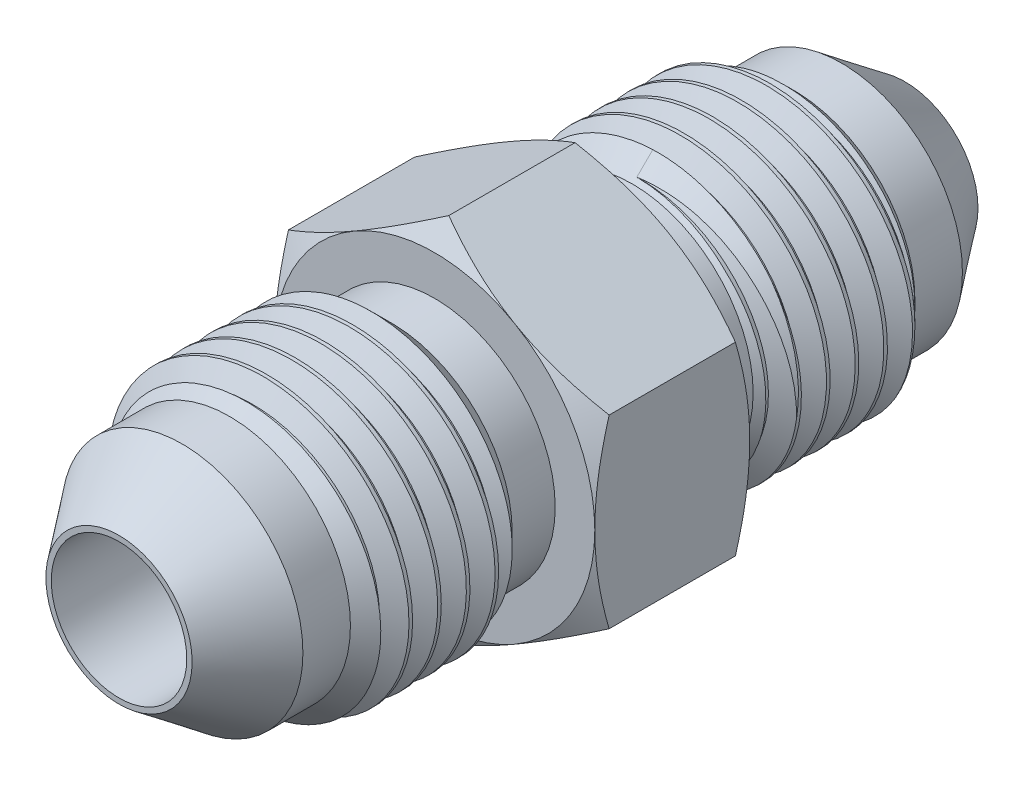
SolidWorks part; units mm, degrees
material "Brass"
ref_plane "Front Plane" through (0, 0, 0) normal (0, 0, 1) x (1, 0, 0)
ref_plane "Top Plane" through (0, 0, 0) normal (0, 1, 0) x (1, 0, 0)
ref_plane "Right Plane" through (0, 0, 0) normal (1, 0, 0) x (0, 0, -1)
sketch "Sketch1" plane through (0, 0, 0) normal (1, 0, 0) x (0, 0, -1)
  line L0 (-17.4, 0) -> (17.4, 0) construction
  line L1 (-17.4, 5.3467) -> (-17.4, -5.3467) construction
  line L2 (-3.43, -7.1) -> (-3.43, 7.1) construction
  line L3 (17.4, 5.3467) -> (17.4, -5.3467) construction
  line L4 (3.43, -7.1) -> (3.43, 7.1) construction
  line L5 (-5.335, -6.35) -> (-5.335, 6.35) construction
  line L6 (12.4978, -6.35) -> (12.4978, 6.35) construction
  line L7 (12.4978, 6.35) -> (5.335, 6.35) construction
  line L8 (5.335, -6.35) -> (5.335, 6.35) construction
  line L10 (0, 3) -> (0, -3) construction
  line L11 (-12.4978, 6.35) -> (-12.4978, -6.35) construction
  line L12 (-12.4978, 6.35) -> (-5.335, 6.35) construction
  line L14 (-5.335, 5.3467) -> (-3.43, 5.3467) construction
  line L15 (5.335, 5.3467) -> (3.43, 5.3467) construction
  line L16 (-12.4978, 5.3467) -> (-17.4, 5.3467) construction
  line L17 (12.4978, 5.3467) -> (17.4, 5.3467) construction
  point P12 (3.43, 0)
  point P13 (-3.43, 0)
  point P17 (12.4978, 0)
  point P25 (-12.4978, 0)
  point P36 (-5.335, 0)
  point P39 (5.335, 0)
  dimension "Hex Body" = 14.2
  dimension "Length" = 34.8
  dimension "Orifice" = 6
  dimension "Straight Length" = 13.97
  dimension "Straight Diameter" = 10.6934
  dimension "Thread OD" = 12.7
  dimension "Thread Length" = 7.1628
  dimension "Thread Offset" = 1.905
sketch "Sketch2" plane through (0, 0, 0) normal (1, 0, 0) x (0, 0, -1)
  line L1 (-13.6884, 6.4875) -> (-13.0534, 5.3876) construction
  line L7 (-13.0534, 5.3876) -> (-12.4184, 6.4875) construction
  line L10 (-12.4184, 6.4875) -> (-13.6884, 6.4875) construction
  line L13 (-13.609, 6.35) -> (-12.4978, 6.35) construction
  line L16 (-13.0534, 6.4875) -> (-13.0534, 6.35) construction
  line L21 (-13.0534, 6.35) -> (-13.0534, 5.5251) construction
  line L23 (-17.4, 3.2385) -> (-14.6023, 5.3467)
  line L24 (-17.4, 5.3467) -> (-17.4, -5.3467) construction
  line L25 (-12.4978, 5.3467) -> (-17.4, 5.3467) construction
  line L26 (-14.6023, 5.3467) -> (-12.4978, 5.3467)
  line L27 (-12.4978, 5.3467) -> (-11.4945, 6.35)
  line L28 (-12.4978, 6.35) -> (-5.335, 6.35) construction
  line L29 (-11.4945, 6.35) -> (-6.3383, 6.35)
  line L34 (-6.3383, 6.35) -> (-5.335, 5.3467)
  line L35 (-5.335, 5.3467) -> (-3.43, 5.3467)
  line L36 (-3.43, 5.3467) -> (-3.43, 7.1)
  line L37 (-17.4, 0) -> (17.4, 0) construction
  line L38 (-17.4, 3.2385) -> (-17.4, 3)
  line L39 (-17.4, 3) -> (17.4, 3)
  line L40 (-3.43, 7.1) -> (-2.6102, 8.52)
  line L46 (-2.6102, 8.52) -> (2.6102, 8.52)
  line L48 (-17.4, 0) -> (17.4, 0) construction
  line L49 (17.4, 3) -> (17.4, 3.2385)
  line L50 (17.4, 5.3467) -> (17.4, -5.3467) construction
  line L51 (17.4, 3.2385) -> (14.6023, 5.3467)
  line L52 (12.4978, 5.3467) -> (17.4, 5.3467) construction
  line L53 (14.6023, 5.3467) -> (12.4978, 5.3467)
  line L54 (12.4978, 5.3467) -> (11.4945, 6.35)
  line L55 (12.4978, 6.35) -> (5.335, 6.35) construction
  line L56 (11.4945, 6.35) -> (6.3383, 6.35)
  line L57 (6.3383, 6.35) -> (5.335, 5.3467)
  line L58 (5.335, 5.3467) -> (3.43, 5.3467)
  line L59 (3.43, 5.3467) -> (3.43, 7.1)
  line L60 (3.43, 7.1) -> (2.6102, 8.52)
  line L61 (-13.0534, 5.5251) -> (-13.0534, 5.3876) construction
  line L62 (-13.1328, 5.5251) -> (-12.974, 5.5251)
  line L63 (-13.6487, 6.4187) -> (-12.4581, 6.4187)
  line L64 (-12.974, 5.5251) -> (-12.4581, 6.4187)
  line L65 (-13.1328, 5.5251) -> (-13.6487, 6.4187)
  line L66 (12.4184, 6.4875) -> (13.0534, 5.3876) construction
  line L67 (13.0534, 5.3876) -> (13.6884, 6.4875) construction
  line L68 (13.6884, 6.4875) -> (12.4184, 6.4875) construction
  line L69 (12.4978, 6.35) -> (13.609, 6.35) construction
  line L70 (13.0534, 6.4875) -> (13.0534, 6.35) construction
  line L71 (13.0534, 6.35) -> (13.0534, 5.5251) construction
  line L72 (13.0534, 5.5251) -> (13.0534, 5.3876) construction
  line L73 (12.974, 5.5251) -> (13.1328, 5.5251)
  line L74 (12.4581, 6.4187) -> (13.6487, 6.4187)
  line L75 (13.1328, 5.5251) -> (13.6487, 6.4187)
  line L76 (12.974, 5.5251) -> (12.4581, 6.4187)
  line L77 (-17.4, 3.9688) -> (-17.4, -3.9688) construction
  line L78 (17.4, 3.9688) -> (17.4, -3.9688) construction
  point P49 (-13.0534, 6.4187)
  point P63 (13.0534, 6.4187)
  dimension "D1" = 45
  dimension "Flared Angle" = 37
  dimension "Flared Height" = 2.1082
  dimension "D4" = 30
  dimension "D5" = 17.04
  dimension "Thread Pitch" = 1.27
  dimension "D3" = 0.1588
  dimension "D6" = 1.27
  dimension "D7" = 0.1588
  dimension "For Tube OD" = 7.9375
sketch "Sketch4" plane through (0, 0, 0) normal (1, 0, 0) x (0, 0, -1)
  line L57 (-17.4, 3.2385) -> (-17.4, 3) construction
  line L58 (-17.4, 3.2385) -> (-14.6023, 5.3467) construction
  line L59 (-14.6023, 5.3467) -> (-12.4978, 5.3467) construction
  line L60 (-12.4978, 5.3467) -> (-11.4945, 6.35) construction
  line L61 (-11.4945, 6.35) -> (-6.3383, 6.35) construction
  line L62 (-6.3383, 6.35) -> (-5.335, 5.3467) construction
  line L63 (-5.335, 5.3467) -> (-3.43, 5.3467) construction
  line L64 (-3.43, 5.3467) -> (-3.43, 7.1) construction
  line L65 (-3.43, 7.1) -> (-2.6102, 8.52) construction
  line L66 (-2.6102, 8.52) -> (2.6102, 8.52) construction
  line L67 (3.43, 7.1) -> (2.6102, 8.52) construction
  line L68 (3.43, 5.3467) -> (3.43, 7.1) construction
  line L69 (5.335, 5.3467) -> (3.43, 5.3467) construction
  line L70 (6.3383, 6.35) -> (5.335, 5.3467) construction
  line L71 (11.4945, 6.35) -> (6.3383, 6.35) construction
  line L72 (12.4978, 5.3467) -> (11.4945, 6.35) construction
  line L73 (14.6023, 5.3467) -> (12.4978, 5.3467) construction
  line L74 (17.4, 3.2385) -> (14.6023, 5.3467) construction
  line L75 (17.4, 3) -> (17.4, 3.2385) construction
  line L76 (-17.4, 3) -> (17.4, 3) construction
  line L77 (-17.4, 3.2385) -> (-17.4, 3)
  line L78 (-17.4, 3.2385) -> (-14.6023, 5.3467)
  line L79 (-14.6023, 5.3467) -> (-12.4978, 5.3467)
  line L80 (-12.4978, 5.3467) -> (-11.4945, 6.35)
  line L81 (-11.4945, 6.35) -> (-6.3383, 6.35)
  line L82 (-6.3383, 6.35) -> (-5.335, 5.3467)
  line L83 (-5.335, 5.3467) -> (-3.43, 5.3467)
  line L84 (-3.43, 5.3467) -> (-3.43, 7.1)
  line L85 (-3.43, 7.1) -> (-2.6102, 8.52)
  line L86 (-2.6102, 8.52) -> (2.6102, 8.52)
  line L87 (3.43, 7.1) -> (2.6102, 8.52)
  line L88 (3.43, 5.3467) -> (3.43, 7.1)
  line L89 (5.335, 5.3467) -> (3.43, 5.3467)
  line L90 (6.3383, 6.35) -> (5.335, 5.3467)
  line L91 (11.4945, 6.35) -> (6.3383, 6.35)
  line L92 (12.4978, 5.3467) -> (11.4945, 6.35)
  line L93 (14.6023, 5.3467) -> (12.4978, 5.3467)
  line L94 (17.4, 3.2385) -> (14.6023, 5.3467)
  line L95 (17.4, 3) -> (17.4, 3.2385)
  line L96 (-17.4, 3) -> (17.4, 3)
revolve "Revolve1" add sketch "Sketch4" angle 360 about L0
sketch "Sketch5" plane through (0, 0, 3.43) normal (0, 0, 1) x (1, 0, 0)
  line L1 (0, 8.1984) -> (-7.1, 4.0992)
  line L2 (-7.1, 4.0992) -> (-7.1, -4.0992)
  line L3 (-7.1, -4.0992) -> (0, -8.1984)
  line L4 (0, -8.1984) -> (7.1, -4.0992)
  line L5 (7.1, -4.0992) -> (7.1, 4.0992)
  line L6 (7.1, 4.0992) -> (0, 8.1984)
  circle A0 centre (0, 0) radius 7.1 construction
extrude "Cut-Extrude1" cut sketch "Sketch5" against normal up to vertex (6.86 mm away) flip side to cut up to point (0, 7.1, -3.43)
sketch "Drawing Ref Right" plane through (0, 0, 0) normal (1, 0, 0) x (0, 0, -1)
  line L7 (12.4978, -6.35) -> (12.4978, 6.35) construction
  line L8 (-12.4978, 6.35) -> (-12.4978, -6.35) construction
  line L9 (12.4978, -6.35) -> (12.4978, 6.35) construction
  line L10 (-12.4978, 6.35) -> (-12.4978, -6.35) construction
  line L11 (11.4945, 6.35) -> (6.3383, 6.35) construction
  line L12 (-11.4945, 6.35) -> (-6.3383, 6.35) construction
  line L13 (-17.4, 0) -> (17.4, 0) construction
  line L14 (-17.4, 0) -> (17.4, 0) construction
  line L15 (11.4945, 6.35) -> (6.3383, 6.35) construction
  line L16 (-11.4945, 6.35) -> (-6.3383, 6.35) construction
  line L17 (11.4945, -6.35) -> (6.3383, -6.35) construction
  line L18 (-11.4945, -6.35) -> (-6.3383, -6.35) construction
  point P14 (-9.3228, -6.35)
  dimension "D1" = 3.175
sketch "Split Lines" plane through (0, 0, 0) normal (1, 0, 0) x (0, 0, -1)
  line L0 (12.4978, -6.35) -> (12.4978, 6.35) construction
  line L1 (5.335, -6.35) -> (5.335, 6.35) construction
  line L2 (-5.335, -6.35) -> (-5.335, 6.35) construction
  line L3 (-12.4978, 6.35) -> (-12.4978, -6.35) construction
  line L4 (12.4978, -6.35) -> (12.4978, 6.35)
  line L5 (5.335, -6.35) -> (5.335, 6.35)
  line L6 (-5.335, -6.35) -> (-5.335, 6.35)
  line L7 (-12.4978, 6.35) -> (-12.4978, -6.35)
split "Split1" trim tools "Split Lines" bodies to split 105 resulting bodies 115 116 117 118 119
sketch "Sketch7" plane through (0, 0, 12.4978) normal (0, 0, 1) x (1, 0, 0)
  circle A0 centre (0, 0) radius 6.35
curve "Helix/Spiral1" pitch 1.27 height 8.4328 radius 6.35 centre (0, 0, 12.4978) axis (0, 0, -1) start towards (0, 1, 0)
sketch "Sketch8" plane through (0, 0, 0) normal (1, 0, 0) x (0, 0, -1)
  line L0 (-13.1328, 5.5251) -> (-12.974, 5.5251) construction
  line L1 (-13.1328, 5.5251) -> (-13.6487, 6.4187) construction
  line L2 (-13.6487, 6.4187) -> (-12.4581, 6.4187) construction
  line L3 (-12.974, 5.5251) -> (-12.4581, 6.4187) construction
  line L4 (-13.1328, 5.5251) -> (-12.974, 5.5251)
  line L5 (-13.1328, 5.5251) -> (-13.6487, 6.4187)
  line L6 (-13.6487, 6.4187) -> (-12.4581, 6.4187)
  line L7 (-12.974, 5.5251) -> (-12.4581, 6.4187)
sweep "Cut-Sweep1" cut profiles "Sketch8" path "Helix/Spiral1" align with end faces yes
sketch "Sketch9" plane through (0, 0, -12.4978) normal (0, 0, -1) x (-1, 0, 0)
  circle A1 centre (0, 0) radius 6.35
curve "Helix/Spiral2" pitch 1.27 height 8.4328 radius 6.35 centre (0, 0, -12.4978) axis (0, 0, 1) start towards (0, 1, 0)
sketch "Sketch10" plane through (0, 0, 0) normal (1, 0, 0) x (0, 0, -1)
  line L0 (12.974, 5.5251) -> (13.1328, 5.5251) construction
  line L1 (12.974, 5.5251) -> (12.4581, 6.4187) construction
  line L2 (12.4581, 6.4187) -> (13.6487, 6.4187) construction
  line L3 (13.1328, 5.5251) -> (13.6487, 6.4187) construction
  line L4 (12.974, 5.5251) -> (13.1328, 5.5251)
  line L5 (12.974, 5.5251) -> (12.4581, 6.4187)
  line L6 (12.4581, 6.4187) -> (13.6487, 6.4187)
  line L7 (13.1328, 5.5251) -> (13.6487, 6.4187)
sweep "Cut-Sweep2" cut profiles "Sketch10" path "Helix/Spiral2" align with end faces yes
combine bodies "Combine1" operation type add bodies to combine 115 116 118 120 121
equation "\"D5@Sketch2\"=\"Hex Body@Sketch1\"*1.2"
equation "\"D3@Sketch2\" = \"Thread Pitch@Sketch2\" / 8"
equation "\"D6@Sketch2\"=\"Thread Pitch@Sketch2\""
equation "\"D7@Sketch2\"=\"D6@Sketch2\"/8"
equation "\"D3@Helix/Spiral1\"=\"Thread Length@Sketch1\"+\"Thread Pitch@Sketch2\""
equation "\"D4@Helix/Spiral1\"=\"Thread Pitch@Sketch2\""
equation "\"D3@Helix/Spiral2\"=\"Thread Length@Sketch1\"+\"Thread Pitch@Sketch2\""
equation "\"D4@Helix/Spiral2\"=\"Thread Pitch@Sketch2\""
equation "\"D1@Drawing Ref Right\"=\"Thread Pitch@Sketch2\"*2.5"
